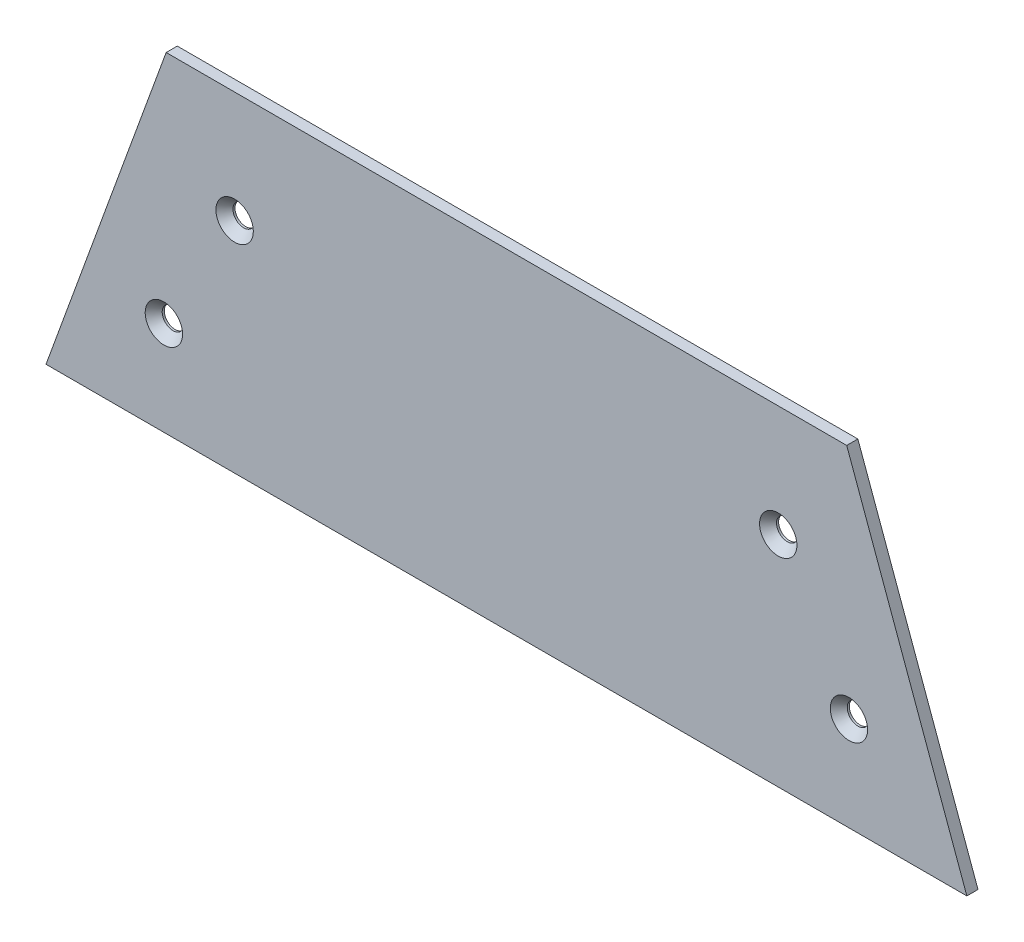
SolidWorks part; units mm, degrees
material "Delrin 2700 NC010, Low Viscosity Acetal Copolymer (SS)"
ref_plane "Front Plane" through (0, 0, 0) normal (0, 0, 1) x (1, 0, 0)
ref_plane "Top Plane" through (0, 0, 0) normal (0, 1, 0) x (1, 0, 0)
ref_plane "Right Plane" through (0, 0, 0) normal (1, 0, 0) x (0, 0, -1)
sketch "Sketch1" plane through (0, 0, 0) normal (0, 0, 1) x (1, 0, 0)
  line L1 (-97.6385, -35) -> (97.6385, -35)
  line L2 (-97.6385, -35) -> (-97.6385, 35)
  line L3 (-97.6385, 35) -> (97.6385, 35)
  line L4 (97.6385, -35) -> (97.6385, 35)
  line L5 (-97.6385, -35) -> (97.6385, 35) construction
  line L6 (-97.6385, 35) -> (97.6385, -35) construction
  point P0 (0, 0)
  dimension "D1" = 70
  dimension "D2" = 195.277
extrude "Main" add sketch "Sketch1" along normal mid plane 2.3622
sketch "Sketch2" plane through (0, 0, 1.1811) normal (0, 0, 1) x (1, 0, 0)
  line L0 (-97.6385, 35) -> (-72.1606, 35)
  line L1 (97.6385, 35) -> (-97.6385, 35) construction
  line L2 (-72.1606, 35) -> (-97.6385, -35)
  line L3 (-97.6385, -35) -> (-97.6385, 35)
  line L4 (97.6385, 35) -> (97.6385, -35)
  line L5 (97.6385, -35) -> (72.1606, 35)
  line L6 (72.1606, 35) -> (97.6385, 35)
  dimension "D1" = 20
  dimension "D2" = 20
extrude "AngleCuts" cut sketch "Sketch2" against normal up to next
hole_wizard "BracketHoles" positions "Sketch3" profile "Sketch4" countersink size "#8" standard "ANSI Inch"
sketch "Sketch3" plane through (0, 0, 1.1811) normal (0, 0, 1) x (1, 0, 0)
  line L0 (-97.6385, -35) -> (97.6385, -35) construction
  point P0 (-72.6378, -15)
  point P2 (-57.6378, 11.3816)
  point P4 (57.6378, 11.3816)
  point P6 (72.6378, -15)
  point P19 (57.3723, 11.3816)
  point P20 (0, 0)
  dimension "D1" = 20
  dimension "D2" = 46.3816
  dimension "D3" = 115.2756
  dimension "D4" = 145.2756
  dimension "D5" = 57.6378
  dimension "D6" = 72.6378
sketch "Sketch4" plane through (-72.6378, -15, 1.1811) normal (1, 0, 0) x (0, -1, 0)
  line L0 (0, 0) -> (0, 5)
  line L1 (0, 5) -> (2.286, 5)
  line L2 (2.286, 5) -> (2.286, 1.9285)
  line L3 (2.286, 1.9285) -> (3.9624, 0)
  line L5 (3.9624, 0) -> (0, 0)
  line L6 (-2.286, 1.9285) -> (-3.9624, 0) construction
  line L10 (0, 5) -> (-2.286, 5) construction
  line L11 (0, -6.35) -> (0, 107.95) construction
  dimension "Hole Dia." = 4.572
  dimension "Hole Depth" = 5
  dimension "Near C'Sink Dia." = 7.9248
  dimension "Near C'Sink Angle" = 82
  dimension "Drill Angle" = 180
